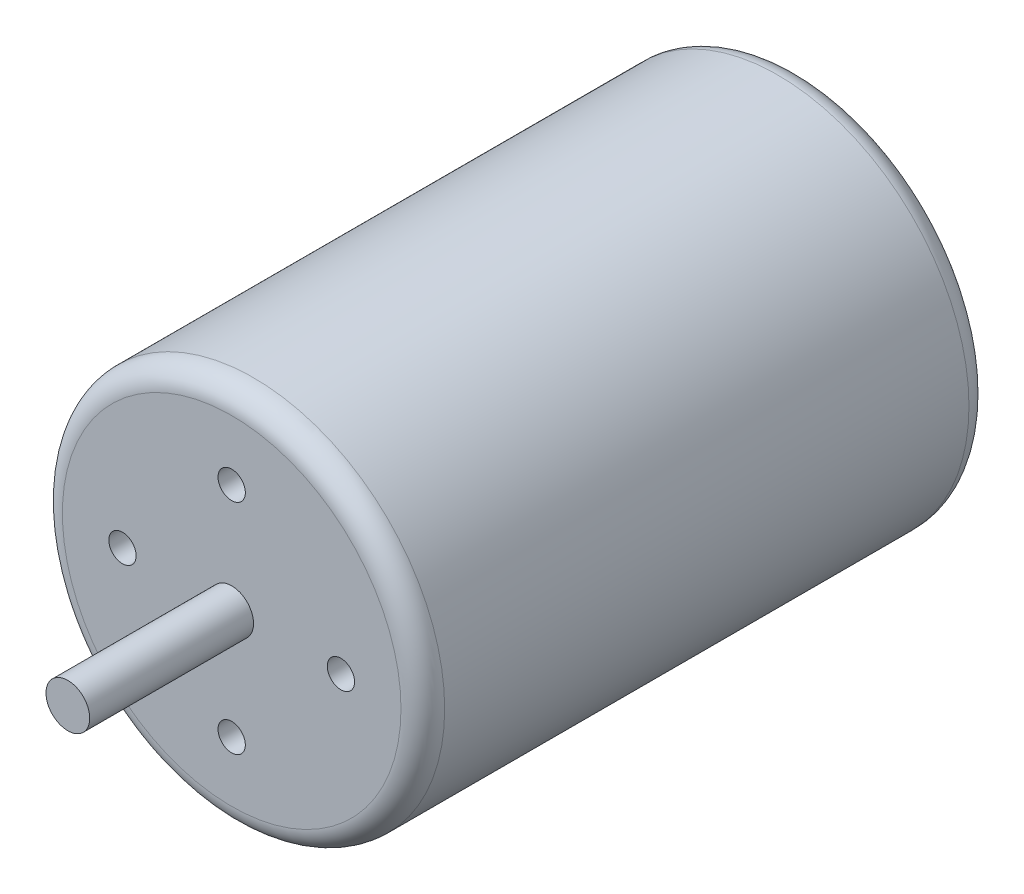
SolidWorks part; units mm, degrees
ref_plane "Front Plane" through (0, 0, 0) normal (0, 0, 1) x (1, 0, 0)
ref_plane "Top Plane" through (0, 0, 0) normal (0, 1, 0) x (1, 0, 0)
ref_plane "Right Plane" through (0, 0, 0) normal (1, 0, 0) x (0, 0, -1)
sketch "Sketch2" plane through (0, 0, 0) normal (0, 0, 1) x (1, 0, 0)
  circle A0 centre (0, 0) radius 22.225
  circle A1 centre (0, 0) radius 2.54
  dimension "D1" = 44.45
  dimension "D2" = 5.08
extrude "Boss-Extrude1" add sketch "Sketch2" against normal blind 66.04 contours A1 | A0 A1 region at (-21.5964, 0, 0) region at (0, 0, 0)
extrude "Boss-Extrude2" add sketch "Sketch2<3>" along normal blind 19.05 contours A1 region at (0, 0, 0)
sketch "Sketch2<3>" plane through (0, 0, 0) normal (0, 0, 1) x (1, 0, 0) same geometry as "Sketch2"
fillet "Fillet1" radius 2.54 2 edges at (22.225, 0, 0) (22.225, 0, -66.04)
sketch "Sketch3" plane through (0, 0, 0) normal (0, 0, 1) x (1, 0, 0)
  circle A0 centre (0, 12.7) radius 1.5875
  circle A1 centre (12.7, 0) radius 1.5875
  circle A2 centre (0, -12.7) radius 1.5875
  circle A3 centre (-12.7, 0) radius 1.5875
  point P12 (0, 0)
  dimension "D1" = 3.175
  dimension "D2" = 12.7
  dimension "D3" = 4
extrude "Cut-Extrude1" cut sketch "Sketch3" against normal blind 6.35
